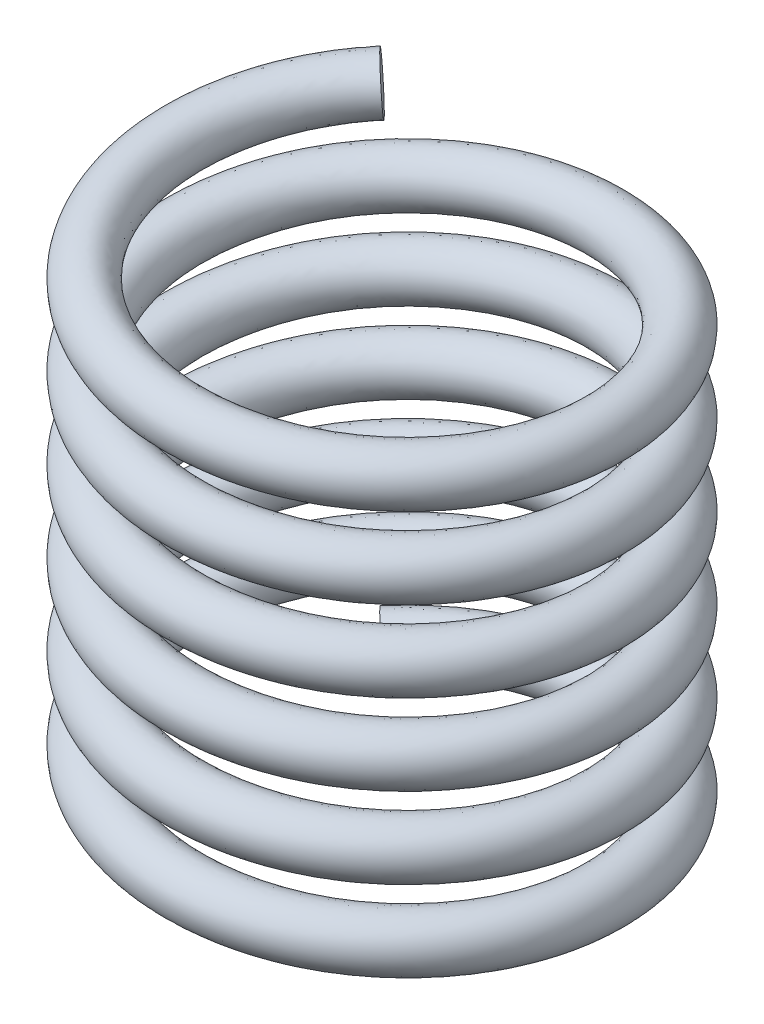
SolidWorks part; units mm, degrees
note: '?' marks a value the reader was unsure of.
material "Cast Stainless Steel"
ref_plane "Front" through (0, 0, 0) normal (0, 0, 1) x (1, 0, 0)
ref_plane "Top" through (0, 0, 0) normal (0, 1, 0) x (1, 0, 0)
ref_plane "Right" through (0, 0, 0) normal (1, 0, 0) x (0, 0, -1)
sketch "Sketch1" plane through (0, 0, 0) normal (0, 1, 0) x (1, 0, 0)
  circle A0 centre (0, 0) radius 2
curve "Helix/Spiral2" pitch 0.7667 height 4.6 turns 6
ref_plane "Plane1" through (-1.4142, 0, -1.4142) normal (0.7058, 0.0609, -0.7058) x (-0.7084, 0.0607, -0.7032)
sketch "Sketch3" plane through (-1.4142, 0, -1.4142) normal (0.7058, 0.0609, -0.7058) x (-0.7084, 0.0607, -0.7032)
  circle A0 centre (-0.0007, -0.0001) radius 0.25
sweep "Sweep1" add profiles "Sketch3" path "Helix/Spiral2"
ref_plane "Plane2" through (0, 0, 0) normal (0, 0, 1) x (1, 0, 0)
ref_axis "Axis2" through (0, 50, 0) along (0, -1, 0)?
